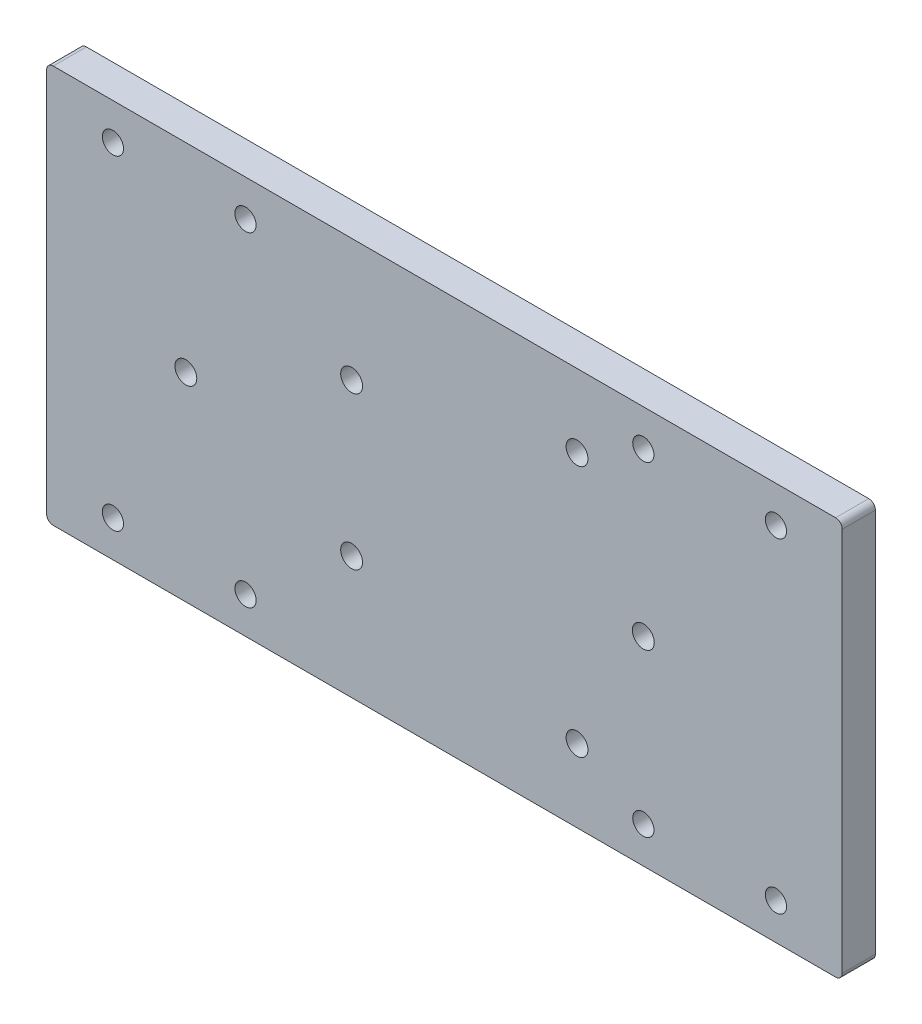
SolidWorks part; units mm, degrees
ref_plane "前视基准面" through (0, 0, 0) normal (0, 0, 1) x (1, 0, 0)
ref_plane "上视基准面" through (0, 0, 0) normal (0, 1, 0) x (1, 0, 0)
ref_plane "右视基准面" through (0, 0, 0) normal (1, 0, 0) x (0, 0, -1)
other "Configuration Table"
sketch "草图1" plane through (0, 0, 0) normal (0, 0, 1) x (1, 0, 0)
  line L0 (12, -49) -> (12, 0) construction
  line L1 (20, 5.5) -> (-100, 5.5)
  line L2 (20, 5.5) -> (20, -54.5)
  line L3 (20, -54.5) -> (-100, -54.5)
  line L4 (-100, 5.5) -> (-100, -54.5)
  line L5 (12, -52.5) -> (12, -45.5) construction
  line L6 (12, -3.5) -> (12, 3.5) construction
  line L7 (12, -24.5) -> (23.0806, -24.5) construction
  point P12 (12, -24.5)
  dimension "D3" = 20
  dimension "D1" = 60
  dimension "D2" = 120
extrude "凸台-拉伸1" add sketch "草图1" along normal blind 5
sketch "草图2" plane through (0, 0, 5) normal (0, 0, 1) x (1, 0, 0)
  circle A0 centre (-54, -13) radius 1.65
  circle A1 centre (-79, -24.5) radius 1.65
  circle A3 centre (-54, -36) radius 1.65
  dimension "D1" = 3.3
extrude "切除-拉伸1" cut sketch "草图2" against normal up to next
sketch "草图4" plane through (0, 0, 0) normal (0, 0, -1) x (-1, 0, 0)
  circle A0 centre (90, 0) radius 1.6
  circle A1 centre (70, 0) radius 1.6
  circle A2 centre (70, -49) radius 1.6
  circle A3 centre (90, -49) radius 1.6
  circle A4 centre (10, -49) radius 1.6
  circle A5 centre (-10, -49) radius 1.6
  circle A6 centre (-10, 0) radius 1.6
  circle A7 centre (10, 0) radius 1.6
  dimension "D1" = 3.2
extrude "切除-拉伸2" cut sketch "草图4" against normal up to next
sketch "草图5" plane through (0, 0, 5) normal (0, 0, 1) x (1, 0, 0)
  line L0 (-20, -54.5) -> (-20, 5.5) construction
  line L1 (-100, -54.5) -> (20, -54.5) construction
  line L2 (20, 5.5) -> (-100, 5.5) construction
  line L3 (20, -54.5) -> (20, 5.5) construction
  line L4 (-10, -24.5) -> (20, -24.5) construction
  circle A0 centre (-20, -43.5) radius 1.65
  circle A1 centre (-10, -24.5) radius 1.65
  circle A2 centre (-20, -5.5) radius 1.65
  dimension "D4" = 3.3
  dimension "D1" = 40
  dimension "D2" = 11
  dimension "D3" = 11
  dimension "D5" = 10
extrude "切除-拉伸3" cut sketch "草图5" against normal up to next
fillet "圆角1" radius 1 4 edges at (-100, -54.5, 2.5) (-100, 5.5, 2.5) (20, -54.5, 2.5) (20, 5.5, 2.5)
